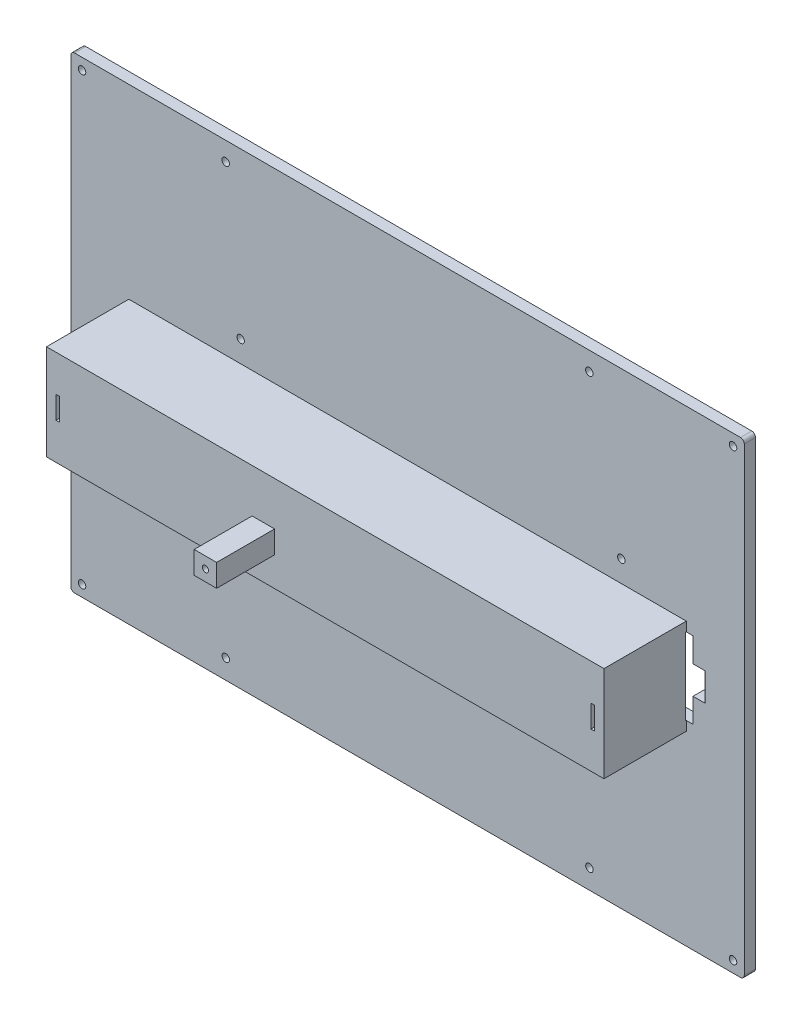
SolidWorks part; units mm, degrees
ref_plane "前视基准面" through (0, 0, 0) normal (0, 0, 1) x (1, 0, 0)
ref_plane "上视基准面" through (0, 0, 0) normal (0, 1, 0) x (1, 0, 0)
ref_plane "右视基准面" through (0, 0, 0) normal (1, 0, 0) x (0, 0, -1)
sketch "草图1" plane through (0, 0, 0) normal (0, 0, 1) x (1, 0, 0)
  line L1 (-90, 62.5) -> (90, 62.5)
  line L2 (-90, 62.5) -> (-90, -62.5)
  line L3 (-90, -62.5) -> (90, -62.5)
  line L4 (90, 62.5) -> (90, -62.5)
  line L5 (-90, 62.5) -> (90, -62.5) construction
  line L6 (-90, -62.5) -> (90, 62.5) construction
  point P0 (0, 0)
  dimension "D1" = 125
  dimension "D2" = 180
extrude "凸台-拉伸1" add sketch "草图1" along normal blind 3
sketch "草图7" plane through (0, 0, 0) normal (0, 0, -1) x (-1, 0, 0)
  line L1 (-72, 10.25) -> (72, 10.25)
  line L2 (-72, 10.25) -> (-72, -10.25)
  line L3 (-72, -10.25) -> (72, -10.25)
  line L4 (72, 10.25) -> (72, -10.25)
  line L5 (0, 0) -> (72.729, 0) construction
  line L8 (0, 0) -> (0, -50.9103) construction
  dimension "D1" = 20.5
  dimension "D2" = 144
extrude "电池位切除-拉伸3" cut sketch "草图7" against normal up to next
sketch "草图8" plane through (0, 0, 3) normal (0, 0, 1) x (1, 0, 0)
  line L12 (72, 10.25) -> (72, -10.25) construction
  line L13 (-74.5, 12.75) -> (74.5, 12.75)
  line L14 (-74.5, 12.75) -> (-74.5, -12.75)
  line L15 (-74.5, -12.75) -> (74.5, -12.75)
  line L16 (74.5, 12.75) -> (74.5, -12.75)
  line L17 (-72, -10.25) -> (-72, 10.25) construction
  line L18 (-72, 10.25) -> (72, 10.25) construction
  line L19 (72, -10.25) -> (-72, -10.25) construction
  line L20 (-72, 10.25) -> (72, 10.25)
  line L21 (72, -10.25) -> (-72, -10.25)
  line L22 (72, 10.25) -> (72, -10.25)
  line L23 (-72, -10.25) -> (-72, 10.25) construction
  line L24 (-72, -10.25) -> (-72, 10.25)
  dimension "D1" = 2.5
  dimension "D2" = 2.5
  dimension "D3" = 2.5
  dimension "D4" = 2.5
extrude "凸台-拉伸2" add sketch "草图8" along normal blind 22
sketch "草图9" plane through (0, 0, 25) normal (0, 0, 1) x (1, 0, 0)
  line L0 (74.5, 12.75) -> (-74.5, 12.75) construction
  line L5 (74.5, 12.75) -> (-74.5, 12.75)
  line L6 (-74.5, -12.75) -> (74.5, -12.75) construction
  line L7 (-74.5, -12.75) -> (74.5, -12.75)
  line L8 (74.5, -12.75) -> (74.5, 12.75) construction
  line L9 (74.5, -12.75) -> (74.5, 12.75)
  line L10 (-74.5, 12.75) -> (-74.5, -12.75) construction
  line L11 (-74.5, 12.75) -> (-74.5, -12.75)
extrude "凸台-拉伸3" add sketch "草图9" against normal blind 2.5
sketch "草图4" plane through (0, 0, 0) normal (0, 0, -1) x (-1, 0, 0)
  line L0 (72, -10.25) -> (72, 10.25) construction
  line L5 (72, 0) -> (84.6307, 0) construction
  line L10 (83.2374, -53.4277) -> (79.3374, -53.4277) construction
  line L11 (83.2374, -49.6277) -> (83.2374, -53.4277) construction
  line L12 (79.3374, -49.6277) -> (83.2374, -49.6277) construction
  line L29 (72, -4) -> (74.5, -4)
  line L30 (74.5, -4) -> (74.5, 4)
  line L31 (74.5, 4) -> (72, 4)
  line L32 (72, 4) -> (72, -4)
  dimension "D1" = 8
  dimension "D2" = 2.5
extrude "切除-拉伸2" cut sketch "草图4" against normal blind 2 from offset 1.5 offset against normal yes
sketch "草图10" plane through (0, 0, 25) normal (0, 0, 1) x (1, 0, 0)
  line L0 (-16.5366, -1.9347) -> (8.5541, -1.9347) construction
  line L2 (-19.5366, 1.0653) -> (-19.5366, -4.9347)
  line L4 (-13.5366, 1.0653) -> (-13.5366, -4.9347)
  line L5 (-16.5366, -1.9347) -> (-16.5366, 4.0653) construction
  line L6 (0, 0) -> (60.8594, 0) construction
  line L7 (0, 0) -> (0, 60.5) construction
  line L8 (75, 60.5) -> (-75, 60.5) construction
  line L9 (-19.5366, 1.0653) -> (-13.5366, 1.0653)
  line L10 (-19.5366, -4.9347) -> (-13.5366, -4.9347)
  circle A0 centre (-16.5366, -1.9347) radius 0.825
  dimension "D2" = 1.65
  dimension "D1" = 6
extrude "凸台-拉伸4" add sketch "草图10" along normal up to surface (15.5 mm away)
sketch "草图11" plane through (0, 0, 0) normal (0, 0, -1) x (-1, 0, 0)
  circle A0 centre (-48.6147, -57.3) radius 1 construction
  circle A1 centre (-44.6, -18.3) radius 1 construction
  circle A2 centre (57.15, -18.3) radius 1 construction
  circle A3 centre (48.5747, -57.3) radius 1 construction
  circle A4 centre (87, 59.5) radius 1
  circle A5 centre (48.6147, 57.5) radius 1 construction
  circle A6 centre (-57.15, 18.5) radius 1 construction
  circle A7 centre (-48.5747, 57.5) radius 1 construction
  circle A8 centre (-48.6147, -57.3) radius 1
  circle A9 centre (-44.6, -18.3) radius 1
  circle A10 centre (57.15, -18.3) radius 1
  circle A11 centre (48.5747, -57.3) radius 1
  circle A13 centre (48.6147, 57.5) radius 1
  circle A14 centre (-57.15, 18.5) radius 1
  circle A15 centre (-48.5747, 57.5) radius 1
  circle A16 centre (44.6, 18.5) radius 1 construction
  circle A17 centre (44.6, 18.5) radius 1
  circle A18 centre (87, -59.5) radius 1
  circle A19 centre (-87, -59.5) radius 1
  circle A20 centre (-87, 59.5) radius 1
  dimension "D1" = 2
  dimension "D2" = 2
  dimension "D3" = 2
  dimension "D4" = 2
extrude "固定螺丝切除-拉伸3" cut sketch "草图11" against normal up to next
sketch "草图12" plane through (0, 0, 0) normal (0, 0, -1) x (-1, 0, 0)
  circle A0 centre (-48.5747, 57.5) radius 2
  circle A1 centre (-57.15, 18.5) radius 2
  circle A2 centre (-44.6, -18.3) radius 2
  circle A3 centre (-48.6147, -57.3) radius 2
  circle A4 centre (48.5747, -57.3) radius 2
  circle A5 centre (57.15, -18.3) radius 2
  circle A7 centre (-87, 59.5) radius 2
  circle A8 centre (48.6147, 57.5) radius 2
  circle A9 centre (44.6, 18.5) radius 2
  circle A10 centre (-87, -59.5) radius 2
  circle A11 centre (87, -59.5) radius 2
  circle A12 centre (87, 59.5) radius 2
  dimension "D1" = 4
  dimension "D2" = 4
  dimension "D3" = 4
  dimension "D4" = 4
  dimension "D5" = 4
extrude "固定螺丝凹陷切除-拉伸4" cut sketch "草图12" against normal blind 1.2
fillet "圆角1" radius 1 4 edges at (90, -62.5, 1.5) (-90, -62.5, 1.5) (-90, 62.5, 1.5) (90, 62.5, 1.5)
sketch "草图13" plane through (0, 0, 25) normal (0, 0, 1) x (1, 0, 0)
  line L0 (72, 10.25) -> (72, -10.25) construction
  line L1 (72, 3) -> (71, 3)
  line L2 (72, 3) -> (72, -3)
  line L3 (72, -3) -> (71, -3)
  line L4 (71, 3) -> (71, -3)
  line L5 (-72, -10.25) -> (-72, 10.25) construction
  line L6 (-71, 3) -> (-72, 3)
  line L7 (-71, 3) -> (-71, -3)
  line L8 (-71, -3) -> (-72, -3)
  line L9 (-72, 3) -> (-72, -3)
  line L10 (72, 0) -> (59.7453, 0) construction
  dimension "D1" = 1
  dimension "D2" = 6
  dimension "D3" = 1
  dimension "D4" = 6
extrude "切除-拉伸3" cut sketch "草图13" against normal up to next
sketch "草图14" plane through (0, 0, 22.5) normal (0, 0, -1) x (-1, 0, 0)
  line L0 (72, 10.25) -> (-72, 10.25) construction
  line L1 (-71, 10.25) -> (-69, 10.25)
  line L2 (-71, 10.25) -> (-71, 5.25)
  line L3 (-71, 5.25) -> (-69, 5.25)
  line L4 (-69, 10.25) -> (-69, 5.25)
  line L5 (-72, 0) -> (-60.8543, 0) construction
  line L6 (-72, 10.25) -> (-72, -10.25) construction
  line L7 (72, 0) -> (63.4917, 0) construction
  line L8 (69, 10.25) -> (71, 10.25)
  line L9 (69, 10.25) -> (69, 5.75)
  line L10 (69, 5.75) -> (71, 5.75)
  line L11 (71, 10.25) -> (71, 5.75)
  line L12 (72, -10.25) -> (72, 10.25) construction
  line L13 (71, -10.25) -> (71, -5.75)
  line L14 (69, -5.75) -> (71, -5.75)
  line L15 (69, -10.25) -> (69, -5.75)
  line L16 (69, -10.25) -> (71, -10.25)
  line L17 (-69, -10.25) -> (-69, -5.25)
  line L18 (-71, -5.25) -> (-69, -5.25)
  line L19 (-71, -10.25) -> (-71, -5.25)
  line L20 (-71, -10.25) -> (-69, -10.25)
  dimension "D1" = 1
  dimension "D2" = 2
  dimension "D3" = 4.5
  dimension "D4" = 1
  dimension "D5" = 2
  dimension "D6" = 5
extrude "凸台-拉伸5" add sketch "草图14" along normal blind 16
sketch "草图15" plane through (0, 0, 0) normal (0, 0, -1) x (-1, 0, 0)
  line L7 (-72, -10.25) -> (72, -10.25) construction
  line L8 (-76.3, 10.25) -> (-72, 10.25)
  line L9 (-76.3, 10.25) -> (-76.3, 3.75)
  line L10 (-76.3, -10.25) -> (-72, -10.25)
  line L11 (-72, 10.25) -> (-72, -10.25)
  line L12 (-76.3, 3.75) -> (-79.3365, 3.75)
  line L14 (-76.3, -3.75) -> (-79.3365, -3.75)
  line L15 (-79.3365, 3.75) -> (-79.3365, -3.75)
  line L16 (72, 10.25) -> (-72, 10.25) construction
  line L17 (-76.3, -3.75) -> (-76.3, -10.25)
  line L18 (-76.1, -10.05) -> (-76.1, 10.05) construction
  line L19 (-79.2365, 3.5) -> (-79.2365, -3.5) construction
  dimension "D1" = 6.5
  dimension "D2" = 6.5
  dimension "D3" = 0.2
  dimension "D4" = 0.1
extrude "切除-拉伸6" cut sketch "草图15" against normal blind 3.2
sketch "草图17" plane through (0, 0, 0) normal (0, 0, -1) x (-1, 0, 0)
  line L0 (-76.3, 3.75) -> (-79.3365, 3.75) construction
  line L1 (-81.8365, 3.75) -> (-79.3365, 3.75)
  line L2 (-81.8365, 3.75) -> (-81.8365, -3.75)
  line L3 (-81.8365, -3.75) -> (-79.3365, -3.75)
  line L4 (-79.3365, 3.75) -> (-79.3365, -3.75)
  dimension "D1" = 2.5
extrude "切除-拉伸7" cut sketch "草图17" against normal blind 1.5
fillet "圆角2" radius 0.25 26 edges at (-71, 10.25, 14.5) (-69, 10.25, 14.5) (-69, -10.25, 14.5) (-71, -10.25, 14.5) (71, -10.25, 14.5) (69, -10.25, 14.5) (69, 10.25, 14.5) (71, 10.25, 14.5) (-70, 10.25, 6.5) (-71, 8, 6.5) (-70, 5.75, 6.5) (-69, 8, 6.5) (-69, -8, 6.5) (-70, -5.75, 6.5) (-71, -8, 6.5) (-70, -10.25, 6.5) (71, -7.75, 6.5) (70, -5.25, 6.5) (69, -7.75, 6.5) (70, -10.25, 6.5) (70, 10.25, 6.5) (69, 7.75, 6.5) (70, 5.25, 6.5) (71, 7.75, 6.5) (79.3365, 0, 3) (81.8365, 0, 0)
